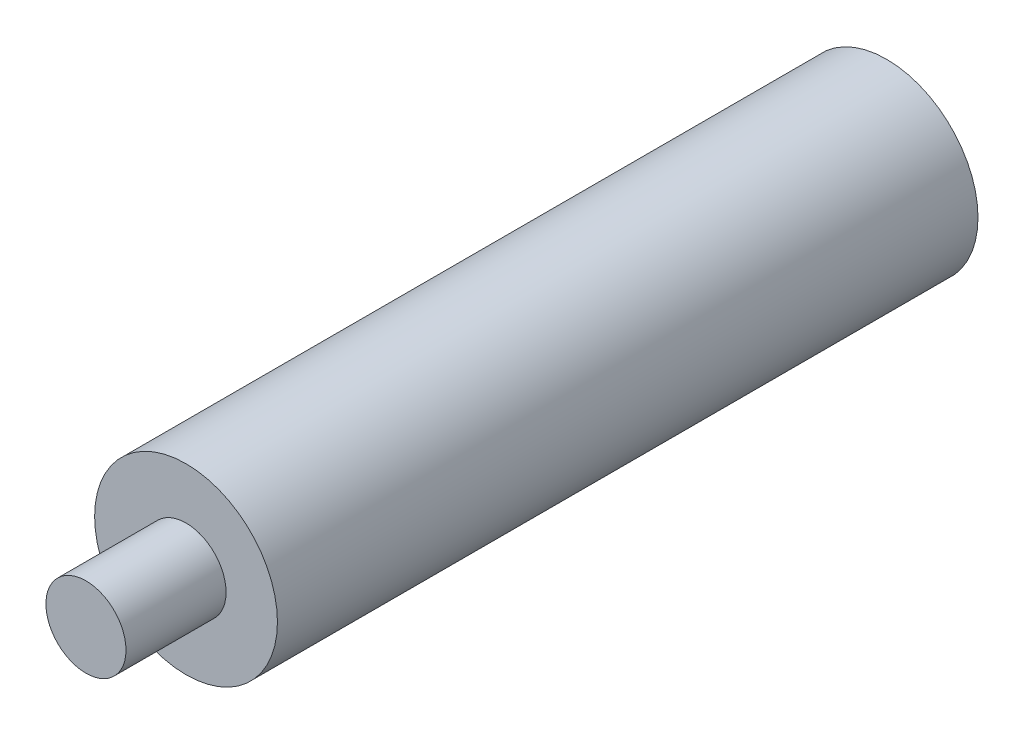
SolidWorks part; units mm, degrees
material "AISI 1020"
ref_plane "前视基准面" through (0, 0, 0) normal (0, 0, 1) x (1, 0, 0)
ref_plane "上视基准面" through (0, 0, 0) normal (0, 1, 0) x (1, 0, 0)
ref_plane "右视基准面" through (0, 0, 0) normal (1, 0, 0) x (0, 0, -1)
sketch "草图2" plane through (0, 0, 0) normal (0, 0, 1) x (1, 0, 0)
  circle A0 centre (0, 0) radius 13.7
  dimension "D1" = 27.4
extrude "凸台-拉伸1" add sketch "草图2" along normal mid plane 105
sketch "草图3" plane through (0, 0, 52.5) normal (0, 0, 1) x (1, 0, 0)
  circle A0 centre (0, 0) radius 6
  dimension "D1" = 12
extrude "凸台-拉伸2" add sketch "草图3" along normal blind 15
hole_wizard "M10 螺纹孔1" positions "草图5" profile "草图4" tap size "M10" standard "GB"
sketch "草图5" plane through (0, 0, -52.5) normal (0, 0, -1) x (-1, 0, 0)
  point P0 (0, 0)
sketch "草图4" plane through (0, 0, -52.5) normal (1, 0, 0) x (0, 1, 0)
  line L0 (0, 0) -> (0, 30.0537)
  line L1 (0, 30.0537) -> (4.25, 27.5)
  line L2 (4.25, 27.5) -> (4.25, 0)
  line L5 (4.25, 0) -> (0, 0)
  line L10 (0, 30.0537) -> (-4.25, 27.5) construction
  line L11 (0, -6.35) -> (0, 107.95) construction
  dimension "螺纹孔钻头直径" = 8.5
  dimension "螺纹孔钻头深度" = 27.5
  dimension "导头角度" = 118
cosmetic thread "孔螺蚊线1"
